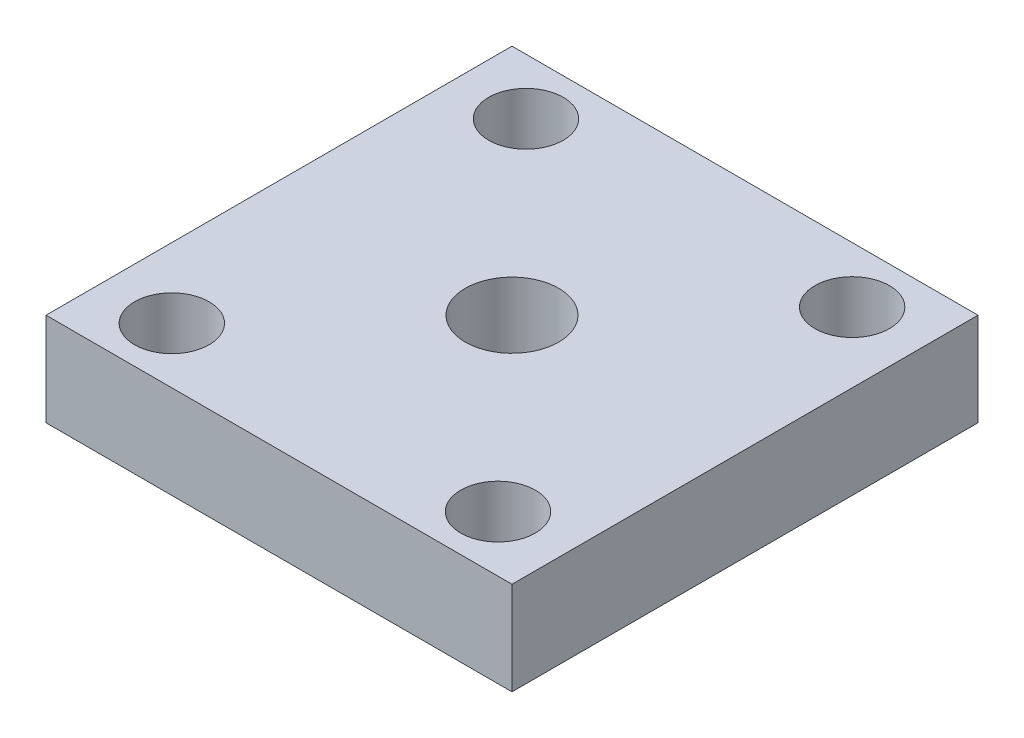
SolidWorks part; units mm, degrees
ref_plane "Front Plane" through (0, 0, 0) normal (0, 0, 1) x (1, 0, 0)
ref_plane "Top Plane" through (0, 0, 0) normal (0, 1, 0) x (1, 0, 0)
ref_plane "Right Plane" through (0, 0, 0) normal (1, 0, 0) x (0, 0, -1)
sketch "Sketch1" plane through (0, 0, 0) normal (0, 1, 0) x (1, 0, 0)
  line L1 (-25, -25) -> (25, -25)
  line L2 (-25, -25) -> (-25, 25)
  line L3 (-25, 25) -> (25, 25)
  line L4 (25, -25) -> (25, 25)
  line L5 (0, 25) -> (0, -25) construction
  line L6 (-25, 0) -> (25, 0) construction
  circle A0 centre (-17.5, 19) radius 1.8
  circle A1 centre (17.5, 19) radius 1.8
  circle A2 centre (17.5, -19) radius 1.8
  circle A3 centre (-17.5, -19) radius 1.8
  circle A4 centre (0, 0) radius 5.01
  point P0 (0, 0)
  dimension "D3" = 3.6
  dimension "D4" = 6
  dimension "D5" = 7.5
  dimension "D6" = 10.02
  dimension "D1" = 50
  dimension "D2" = 50
extrude "Boss-Extrude1" add sketch "Sketch1" along normal blind 10
sketch "Sketch2" plane through (0, 10, 0) normal (0, 1, 0) x (1, 0, 0)
  circle A0 centre (-17.5, 19) radius 4
  circle A1 centre (17.5, 19) radius 4
  circle A2 centre (17.5, -19) radius 4
  circle A3 centre (-17.5, -19) radius 4
  dimension "D1" = 8
  dimension "D2" = 8
  dimension "D3" = 8
  dimension "D4" = 8
extrude "Cut-Extrude1" cut sketch "Sketch2" against normal blind 6
